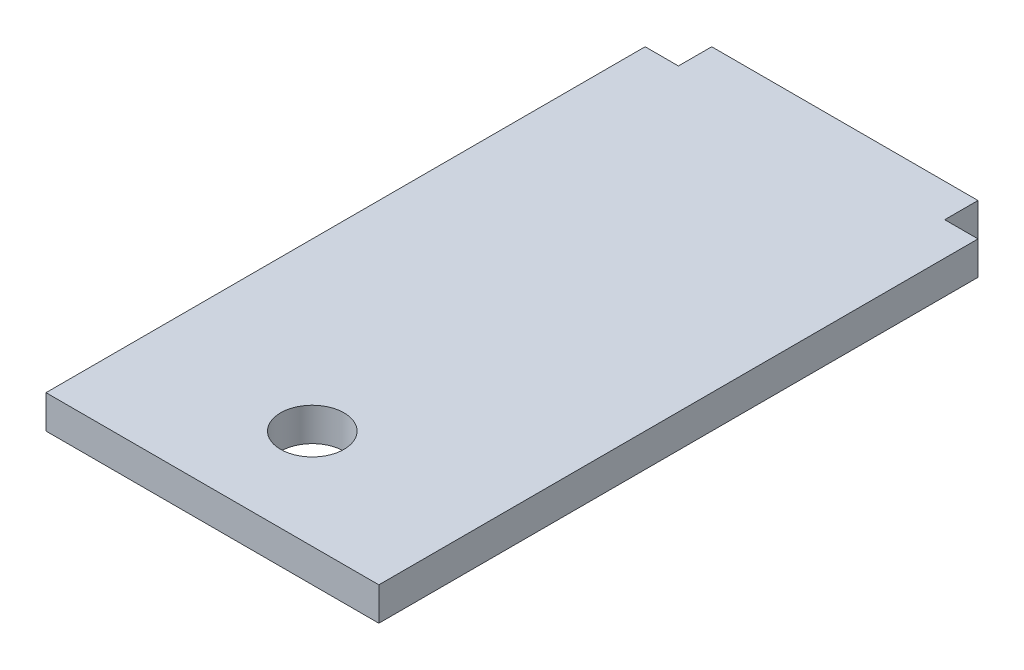
SolidWorks part; units mm, degrees
ref_plane "Front Plane" through (0, 0, 0) normal (0, 0, 1) x (1, 0, 0)
ref_plane "Top Plane" through (0, 0, 0) normal (0, 1, 0) x (1, 0, 0)
ref_plane "Right Plane" through (0, 0, 0) normal (1, 0, 0) x (0, 0, -1)
sketch "Sketch1" plane through (0, 0, 0) normal (0, 1, 0) x (1, 0, 0)
  line L0 (0, 90) -> (5, 90)
  line L1 (0, 0) -> (50, 0)
  line L2 (0, 0) -> (0, 90)
  line L3 (5, 95) -> (45, 95)
  line L4 (50, 0) -> (50, 90)
  line L5 (5, 95) -> (5, 90)
  line L6 (50, 90) -> (45, 90)
  line L7 (45, 90) -> (45, 95)
  line L8 (0, 15) -> (50, 15) construction
  circle A0 centre (25, 15) radius 4.7625
  dimension "D6" = 9.525
  dimension "D1" = 90
  dimension "D2" = 5
  dimension "D3" = 5
  dimension "D4" = 5
  dimension "D5" = 50
  dimension "D7" = 80
extrude "Hammer" add sketch "Sketch1" along normal blind 5
